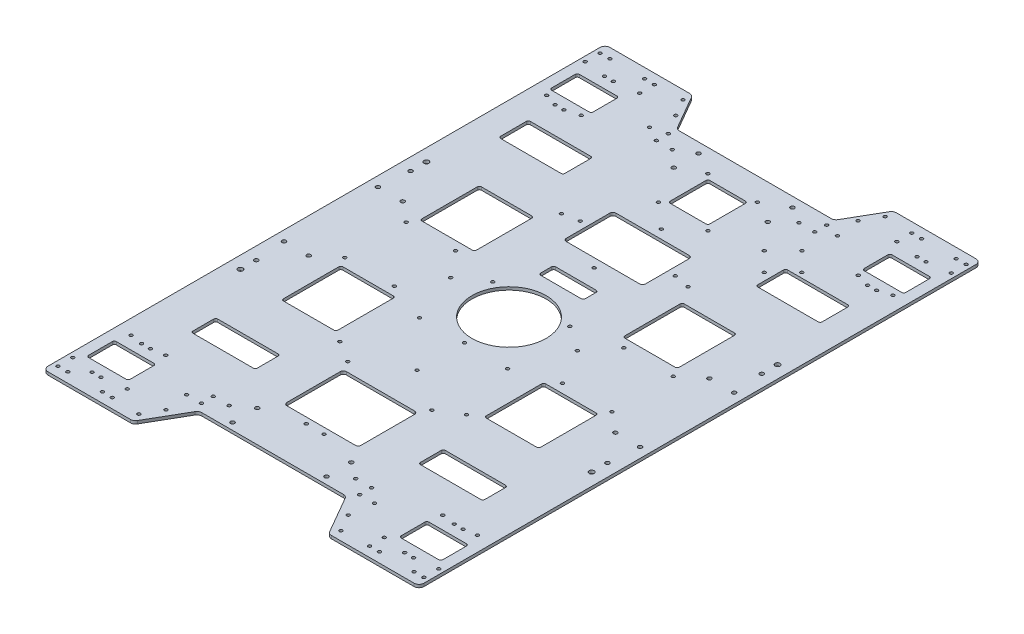
SolidWorks part; units mm, degrees
material "Hexcel AS4C (3000 丝)"
ref_plane "前视基准面" through (0, 0, 0) normal (0, 0, 1) x (1, 0, 0)
ref_plane "上视基准面" through (0, 0, 0) normal (0, 1, 0) x (1, 0, 0)
ref_plane "右视基准面" through (0, 0, 0) normal (1, 0, 0) x (0, 0, -1)
sketch "草图1" plane through (0, 0, 0) normal (0, 1, 0) x (1, 0, 0)
  line L0 (0, 420.0815) -> (0, -400.8011) construction
  line L1 (190, 287) -> (101.545, 287)
  line L2 (190, 287) -> (190, 0)
  line L3 (190, -281) -> (144.0917, -281)
  line L4 (-190, 287) -> (-190, 0)
  line L5 (-313.6361, 0) -> (397.123, 0) construction
  line L6 (144.0917, -281) -> (98.6603, -281)
  line L7 (-101.545, 287) -> (-79.6057, 249)
  line L8 (-79.6057, 249) -> (79.6057, 249)
  line L9 (79.6057, 249) -> (101.545, 287)
  line L10 (-98.6603, -281) -> (-74.4115, -239)
  line L12 (-74.4115, -239) -> (74.4115, -239)
  line L13 (-144.0917, -281) -> (-190, -281)
  line L14 (-101.545, 287) -> (-190, 287)
  line L15 (-98.6603, -281) -> (-144.0917, -281)
  line L17 (190, 0) -> (190, -281)
  line L20 (190, 287) -> (190, -281) construction
  line L22 (74.4115, -239) -> (98.6603, -281)
  line L24 (-190, 0) -> (-190, -281)
  line L26 (-190, 287) -> (-190, -281) construction
  line L44 (229.3448, 326.3448) -> (229.3448, -320.3448) construction
  line L45 (-229.3448, 326.3448) -> (-229.3448, -320.3448) construction
  line L46 (-78.8293, 326.3448) -> (-229.3448, 326.3448) construction
  line L47 (-78.8293, 326.3448) -> (-56.89, 288.3448) construction
  line L48 (-56.89, 288.3448) -> (56.89, 288.3448) construction
  line L49 (56.89, 288.3448) -> (78.8293, 326.3448) construction
  line L50 (229.3448, 326.3448) -> (78.8293, 326.3448) construction
  line L51 (-121.376, -320.3448) -> (-229.3448, -320.3448) construction
  line L52 (229.3448, -320.3448) -> (121.376, -320.3448) construction
  line L53 (-98.6603, -281) -> (-121.376, -320.3448) construction
  line L54 (98.6603, -281) -> (121.376, -320.3448) construction
  line L55 (-132.7338, -261.3276) -> (-144.0917, -281) construction
  line L56 (-132.7338, -261.3276) -> (-97.1273, -199.6552) construction
  line L57 (-97.1273, -199.6552) -> (97.1273, -199.6552) construction
  line L58 (97.1273, -199.6552) -> (132.7338, -261.3276) construction
  line L59 (132.7338, -261.3276) -> (144.0917, -281) construction
  point P0 (0, 0)
  point P10 (-110.2073, -274)
  point P13 (-79.8964, -221.5)
  point P14 (79.8964, -221.5)
  point P16 (110.2073, -274)
  point P21 (200, -271.5)
  point P22 (200, 291.5)
  point P23 (-145.7725, 287)
  point P24 (77.0076, 246.5)
  point P25 (-77.0076, 246.5)
  point P27 (-200, 291.5)
  point P28 (-200, -271.5)
  dimension "D1" = 568
  dimension "D2" = 380
  dimension "D3" = 38
  dimension "D4" = 197.3205
  dimension "D5" = 120
  dimension "D6" = 60
  dimension "D7" = 203.09
  dimension "D8" = 42
  dimension "D9" = 287
extrude "基本板" add sketch "草图1" along normal blind 3
sketch "草图2" plane through (0, 3, 0) normal (0, 1, 0) x (1, 0, 0)
  circle A0 centre (0, 0) radius 37.5
  circle A1 centre (38.9711, 22.5) radius 1.6
  circle A3 centre (0, 0) radius 37.5
  circle A5 centre (0, -45) radius 1.6
  circle A6 centre (0, 0) radius 37.5
  circle A7 centre (-38.9711, 22.5) radius 1.6
  point P14 (0, 0)
  point P16 (0, 0)
  dimension "D1" = 75
  dimension "D3" = 3.2
  dimension "D2" = 45
  dimension "D4" = 3
extrude "云台孔" cut sketch "草图2" against normal blind 3 contours A1 | A0 | A5 | A7 region at (0, 3, 0) region at (38.9711, 3, -22.5) region at (0, 3, 45) region at (-38.9711, 3, -22.5)
sketch "草图8" plane through (0, 3, 0) normal (0, 1, 0) x (1, 0, 0)
  line L0 (0, 320.5112) -> (0, -345.0597) construction
  line L13 (82.5, -149) -> (147.5, -149)
  line L14 (-82.5, -149) -> (-147.5, -149)
  line L15 (-82.5, -149) -> (-82.5, -174)
  line L16 (-82.5, -174) -> (-147.5, -174)
  line L17 (-147.5, -149) -> (-147.5, -174)
  line L18 (-82.5, -149) -> (-147.5, -174) construction
  line L19 (-82.5, -174) -> (-147.5, -149) construction
  line L20 (147.5, -149) -> (147.5, -174)
  line L21 (82.5, -149) -> (147.5, -174) construction
  line L22 (82.5, -174) -> (147.5, -149) construction
  line L23 (82.5, -149) -> (82.5, -174)
  line L24 (82.5, -174) -> (147.5, -174)
  point P12 (-115, -161.5)
  dimension "D1" = 230
  dimension "D5" = 174
  dimension "D7" = 25
  dimension "D8" = 65
extrude "减重过线孔" cut sketch "草图8" against normal blind 3
sketch "草图41" plane through (0, 3, 0) normal (0, 1, 0) x (1, 0, 0)
  line L0 (0, 188.4867) -> (0, -152.142) construction
  line L1 (-206.7892, 0) -> (229.7274, 0) construction
  line L2 (-130, 100) -> (-75, 100)
  line L3 (-130, 100) -> (-130, 40)
  line L4 (-130, 40) -> (-75, 40)
  line L5 (-75, 100) -> (-75, 40)
  line L6 (75, 100) -> (75, 40)
  line L7 (130, 40) -> (75, 40)
  line L8 (130, 100) -> (130, 40)
  line L9 (130, 100) -> (75, 100)
  line L10 (130, -100) -> (75, -100)
  line L11 (130, -100) -> (130, -40)
  line L12 (130, -40) -> (75, -40)
  line L13 (75, -100) -> (75, -40)
  line L14 (-75, -100) -> (-75, -40)
  line L15 (-130, -40) -> (-75, -40)
  line L16 (-130, -100) -> (-130, -40)
  line L17 (-130, -100) -> (-75, -100)
  dimension "D1" = 40
  dimension "D2" = 75
  dimension "D3" = 55
  dimension "D4" = 60
extrude "减重过线孔2" cut sketch "草图41" against normal blind 10
sketch "草图10" plane through (0, 3, 0) normal (0, 1, 0) x (1, 0, 0)
  line L0 (0, 320.3944) -> (0, -95.0551) construction
  line L1 (-162.5, 182) -> (-97.5, 182)
  line L2 (-162.5, 182) -> (-162.5, 152)
  line L3 (-162.5, 152) -> (-97.5, 152)
  line L4 (-97.5, 182) -> (-97.5, 152)
  line L5 (-162.5, 182) -> (-97.5, 152) construction
  line L6 (-162.5, 152) -> (-97.5, 182) construction
  line L7 (162.5, 152) -> (97.5, 152)
  line L8 (97.5, 152) -> (97.5, 182)
  line L9 (97.5, 182) -> (162.5, 182)
  line L11 (162.5, 182) -> (162.5, 152)
  point P0 (-130, 167)
  dimension "D1" = 65
  dimension "D2" = 30
  dimension "D3" = 167
  dimension "D4" = 130
  dimension "D5" = 65
extrude "后电机过线孔" cut sketch "草图10" against normal blind 3
sketch "草图11" plane through (0, 3, 0) normal (0, 1, 0) x (1, 0, 0)
  line L0 (-190, 287) -> (-190, -281) construction
  line L1 (-179, 248) -> (-137, 248)
  line L2 (-179, 248) -> (-179, 220)
  line L3 (-179, 220) -> (-137, 220)
  line L4 (-137, 248) -> (-137, 220)
  line L5 (-179, 248) -> (-137, 220) construction
  line L6 (-179, 220) -> (-137, 248) construction
  line L8 (-158, 274.32) -> (-158, 185.5546) construction
  line L9 (-208.9066, 234) -> (-106.7696, 234) construction
  line L10 (-264.4169, 0) -> (335.6364, 0) construction
  line L11 (0, 360.1922) -> (0, -386.7193) construction
  line L12 (179, 248) -> (179, 220)
  line L13 (179, 220) -> (137, 220)
  line L14 (137, 248) -> (137, 220)
  line L15 (179, 248) -> (137, 248)
  line L16 (179, -248) -> (137, -248)
  line L17 (137, -248) -> (137, -220)
  line L18 (179, -220) -> (137, -220)
  line L19 (179, -248) -> (179, -220)
  line L20 (-179, -248) -> (-179, -220)
  line L21 (-179, -220) -> (-137, -220)
  line L22 (-137, -248) -> (-137, -220)
  line L23 (-179, -248) -> (-137, -248)
  circle A0 centre (-153.5, 259) radius 1.6
  circle A1 centre (-162.5, 259) radius 1.6
  circle A2 centre (-153.5, 209) radius 1.6
  circle A3 centre (-162.5, 209) radius 1.6
  circle A4 centre (153.5, 259) radius 1.6
  circle A5 centre (162.5, 259) radius 1.6
  circle A6 centre (153.5, 209) radius 1.6
  circle A7 centre (162.5, 209) radius 1.6
  circle A8 centre (162.5, -209) radius 1.6
  circle A9 centre (153.5, -209) radius 1.6
  circle A10 centre (162.5, -259) radius 1.6
  circle A11 centre (153.5, -259) radius 1.6
  circle A12 centre (-162.5, -209) radius 1.6
  circle A13 centre (-153.5, -209) radius 1.6
  circle A14 centre (-153.5, -259) radius 1.6
  circle A15 centre (-162.5, -259) radius 1.6
  point P0 (-158, 234)
  dimension "D5" = 3.2
  dimension "D1" = 42
  dimension "D2" = 28
  dimension "D3" = 32
  dimension "D4" = 468
  dimension "D6" = 4.5
  dimension "D7" = 25
extrude "悬挂过孔" cut sketch "草图11" against normal blind 3
sketch "草图13" plane through (0, 3, 0) normal (0, 1, 0) x (1, 0, 0)
  line L0 (79.6057, 249) -> (-79.6057, 249) construction
  line L1 (25, 226) -> (-25, 226) construction
  line L2 (25, 226) -> (25, 176) construction
  line L3 (25, 176) -> (-25, 176) construction
  line L4 (-25, 226) -> (-25, 176) construction
  line L5 (25, 226) -> (-25, 176) construction
  line L6 (25, 176) -> (-25, 226) construction
  circle A0 centre (25, 176) radius 1.6
  circle A1 centre (25, 226) radius 1.6
  circle A2 centre (-25, 226) radius 1.6
  circle A3 centre (-25, 176) radius 1.6
  point P0 (0, 201)
  dimension "D1" = 3.2
  dimension "D2" = 50
  dimension "D3" = 48
  dimension "D4" = 50
extrude "原灯柱固定孔" cut sketch "草图13" against normal blind 3
sketch "草图14" plane through (0, 3, 0) normal (0, 1, 0) x (1, 0, 0)
  line L0 (0, 388.2914) -> (0, -299.2561) construction
  line L1 (79.6057, 249) -> (-79.6057, 249) construction
  line L4 (-74.4115, -239) -> (74.4115, -239) construction
  circle A0 centre (-47.5, 239) radius 2
  circle A1 centre (-47.5, 214) radius 2
  circle A2 centre (47.5, 214) radius 2
  circle A3 centre (47.5, 239) radius 2
  circle A4 centre (-47.5, -207) radius 2
  circle A5 centre (-47.5, -232) radius 2
  circle A6 centre (47.5, -232) radius 2
  circle A7 centre (47.5, -207) radius 2
  dimension "D1" = 25
  dimension "D3" = 4
  dimension "D4" = 4
  dimension "D6" = 4
  dimension "D7" = 4
  dimension "D2" = 10
  dimension "D5" = 47.5
  dimension "D8" = 25
  dimension "D9" = 7
  dimension "D10" = 95
extrude "前后装甲板固定孔" cut sketch "草图14" against normal blind 3
sketch "草图15" plane through (0, 3, 0) normal (0, 1, 0) x (1, 0, 0)
  line L0 (-212.3646, 0) -> (277.5556, 0) construction
  line L1 (190, -281) -> (190, 287) construction
  line L2 (0, 389.4336) -> (0, -385.931) construction
  circle A0 centre (155, 47.5) radius 2
  circle A1 centre (180, 47.5) radius 2
  circle A2 centre (180, -47.5) radius 2
  circle A3 centre (155, -47.5) radius 2
  circle A4 centre (-155, -47.5) radius 2
  circle A5 centre (-180, -47.5) radius 2
  circle A6 centre (-180, 47.5) radius 2
  circle A7 centre (-155, 47.5) radius 2
  dimension "D1" = 25
  dimension "D4" = 4
  dimension "D5" = 4
  dimension "D2" = 10
  dimension "D3" = 47.5
extrude "左右装甲板固定孔" cut sketch "草图15" against normal blind 3
sketch "草图16" plane through (0, 3, 0) normal (0, 1, 0) x (1, 0, 0)
  line L0 (0, 371.6115) -> (0, -351.9198) construction
  line L1 (79.6057, 249) -> (-79.6057, 249) construction
  line L2 (-74.4115, -239) -> (74.4115, -239) construction
  circle A0 centre (-64, 229) radius 1.6
  circle A1 centre (-64, 117) radius 1.6
  circle A2 centre (-64, 5) radius 1.6
  circle A3 centre (-64, -107) radius 1.6
  circle A4 centre (-64, -219) radius 1.6
  circle A5 centre (64, 229) radius 1.6
  circle A6 centre (64, -107) radius 1.6
  circle A7 centre (64, 5) radius 1.6
  circle A8 centre (64, 117) radius 1.6
  circle A9 centre (64, -219) radius 1.6
  dimension "D1" = 20
  dimension "D2" = 3.2
  dimension "D3" = 128
  dimension "D4" = 20
  dimension "D5" = 4
  dimension "D6" = 112
  dimension "D7" = 112
extrude "加强筋固定孔" cut sketch "草图16" against normal blind 3
sketch "草图17" plane through (0, 3, 0) normal (0, 1, 0) x (1, 0, 0)
  line L0 (134.2077, 331.9193) -> (53.2432, 191.6847) construction
  line L1 (101.545, 287) -> (79.6057, 249) construction
  line L2 (190, 287) -> (101.545, 287) construction
  line L3 (0, 408.349) -> (0, -455.0242) construction
  line L4 (-45.0771, -171.5407) -> (-117.5498, -297.067) construction
  line L5 (190, -281) -> (190, 287) construction
  line L6 (-190, -281) -> (-98.6603, -281) construction
  line L7 (-190, 287) -> (-190, -281) construction
  line L8 (-98.6603, -281) -> (-74.4115, -239) construction
  circle A0 centre (95, 264.0096) radius 1.6
  circle A1 centre (102.5, 277) radius 1.6
  circle A3 centre (-95, -258.0096) radius 1.6
  circle A4 centre (-102.5, -271) radius 1.6
  circle A7 centre (102.5, -271) radius 1.6
  circle A8 centre (95, -258.0096) radius 1.6
  circle A10 centre (-102.5, 277) radius 1.6
  circle A11 centre (-95, 264.0096) radius 1.6
  dimension "D2" = 15
  dimension "D4" = 3.2
  dimension "D5" = 3.2
  dimension "D6" = 95
  dimension "D11" = 3.2
  dimension "D12" = 3.2
  dimension "D3" = 95
  dimension "D8" = 10
  dimension "D14" = 10
  dimension "D16" = 15
extrude "前后挡片固定孔" [suppressed] cut sketch "草图17" against normal blind 3
sketch "草图18" plane through (0, 3, 0) normal (0, 1, 0) x (1, 0, 0)
  line L0 (325.6997, 0) -> (-414.0484, 0) construction
  line L1 (167.6795, 77.7768) -> (228.1621, 112.6965) construction
  line L2 (190, -281) -> (190, 287) construction
  line L3 (0, 334.7186) -> (0, -324.7689) construction
  line L4 (190, -281) -> (190, 287) construction
  circle A0 centre (167.6795, 77.7768) radius 1.6
  circle A1 centre (185, 87.7768) radius 1.6
  circle A2 centre (185, -87.7768) radius 1.6
  circle A3 centre (167.6795, -77.7768) radius 1.6
  circle A4 centre (-167.6795, -77.7768) radius 1.6
  circle A5 centre (-185, -87.7768) radius 1.6
  circle A6 centre (-185, 87.7768) radius 1.6
  circle A7 centre (-167.6795, 77.7768) radius 1.6
  point P24 (190, 90.6636)
  dimension "D1" = 30
  dimension "D5" = 3.2
  dimension "D6" = 3.2
  dimension "D2" = 181.3272
  dimension "D3" = 20
  dimension "D4" = 5
extrude "左右挡片固定孔" [suppressed] cut sketch "草图18" against normal blind 3
sketch "草图19" plane through (0, 3, 0) normal (0, 1, 0) x (1, 0, 0)
  line L0 (-190, 287) -> (-190, -281) construction
  line L2 (0, 300.5357) -> (0, -347.8075) construction
  line L3 (-284.3527, 0) -> (241.9977, 0) construction
  circle A0 centre (-177.5, -78) radius 2
  circle A1 centre (-177.5, -94) radius 2.5
  circle A2 centre (-177.5, 94) radius 2.5
  circle A3 centre (-177.5, 78) radius 2
  circle A4 centre (177.5, -94) radius 2.5
  circle A5 centre (177.5, -78) radius 2
  circle A6 centre (177.5, 78) radius 2
  circle A7 centre (177.5, 94) radius 2.5
  dimension "D1" = 12.5
  dimension "D3" = 4
  dimension "D4" = 5
  dimension "D2" = 188
  dimension "D5" = 16
extrude "纵车架固定孔" cut sketch "草图19" against normal blind 3
sketch "草图21" plane through (0, 3, 0) normal (0, 1, 0) x (1, 0, 0)
  line L1 (-84.0108, 0) -> (121.9234, 0) construction
  circle A0 centre (0, -93) radius 1.6
  dimension "D1" = 186
  dimension "D2" = 3.2
extrude "横车架固定孔" cut sketch "草图21" against normal blind 3
sketch "草图30" [suppressed] plane through (0, 3, 0) normal (0, 1, 0) x (1, 0, 0)
  line L0 (0, -74.9086) -> (0, -247.6971) construction
  line L1 (65, -113) -> (65, -157)
  line L2 (-77, -110) -> (-68, -110)
  line L3 (-80, -113) -> (-80, -157)
  line L4 (-77, -160) -> (-68, -160)
  line L5 (-65, -113) -> (-65, -157)
  line L6 (77, -160) -> (68, -160)
  line L7 (80, -113) -> (80, -157)
  line L8 (77, -110) -> (68, -110)
  arc A0 (-68, -110) -> (-65, -113) centre (-68, -113) cw
  arc A1 (-80, -157) -> (-77, -160) centre (-77, -157) ccw
  arc A2 (-68, -160) -> (-65, -157) centre (-68, -157) ccw
  arc A3 (-77, -110) -> (-80, -113) centre (-77, -113) ccw
  arc A4 (77, -110) -> (80, -113) centre (77, -113) cw
  arc A5 (68, -160) -> (65, -157) centre (68, -157) cw
  arc A6 (80, -157) -> (77, -160) centre (77, -157) cw
  arc A7 (68, -110) -> (65, -113) centre (68, -113) ccw
  point P11 (-65, -110)
  point P14 (-80, -160)
  point P17 (-65, -160)
  dimension "D5" = 3
  dimension "D1" = 50
  dimension "D2" = 15
  dimension "D3" = 130
  dimension "D4" = 110
sketch "草图32" plane through (0, 3, 0) normal (0, 1, 0) x (1, 0, 0)
  line L0 (0, -130.9301) -> (0, -286.8622) construction
  line L2 (-34.5, -190) -> (34.5, -190)
  line L3 (-37.5, -187) -> (-37.5, -133)
  line L4 (-34.5, -130) -> (34.5, -130)
  line L5 (37.5, -187) -> (37.5, -133)
  line L6 (0, -130) -> (0, -190) construction
  line L7 (-37.5, -160) -> (37.5, -160) construction
  arc A0 (34.5, -190) -> (37.5, -187) centre (34.5, -187) ccw
  arc A1 (-37.5, -133) -> (-34.5, -130) centre (-34.5, -133) cw
  arc A2 (-34.5, -190) -> (-37.5, -187) centre (-34.5, -187) cw
  arc A3 (34.5, -130) -> (37.5, -133) centre (34.5, -133) cw
  point P3 (0, -160)
  point P9 (37.5, -190)
  point P15 (-37.5, -130)
  point P18 (-37.5, -190)
  dimension "D4" = 3
  dimension "D1" = 60
  dimension "D2" = 75
  dimension "D3" = 160
extrude "切除-拉伸9" cut sketch "草图32" against normal blind 10
sketch "草图33" plane through (0, 3, 0) normal (0, 1, 0) x (1, 0, 0)
  line L1 (-70.5, -55) -> (70.5, -55) construction
  line L2 (-70.5, -55) -> (-70.5, -186) construction
  line L3 (-70.5, -186) -> (70.5, -186) construction
  line L4 (70.5, -55) -> (70.5, -186) construction
  line L5 (0, -186) -> (0, -55) construction
  line L6 (-70.5, -120.5) -> (70.5, -120.5) construction
  line L7 (-60, -180.5) -> (60, -180.5) construction
  line L8 (-60, -180.5) -> (-60, -60.5) construction
  line L9 (-60, -60.5) -> (60, -60.5) construction
  line L10 (60, -180.5) -> (60, -60.5) construction
  line L11 (0, -60.5) -> (0, -180.5) construction
  line L12 (-60, -120.5) -> (60, -120.5) construction
  circle A0 centre (-60, -180.5) radius 1.6 construction
  circle A1 centre (60, -180.5) radius 1.6 construction
  circle A2 centre (60, -60.5) radius 1.6 construction
  circle A3 centre (-60, -60.5) radius 1.6 construction
  circle A4 centre (-42.5, -120.5) radius 1.6
  circle A5 centre (42.5, -120.5) radius 1.6
  point P0 (0, -120.5)
  point P4 (0, -120.5)
  dimension "D6" = 3.2
  dimension "D7" = 3.2
  dimension "D8" = 3.2
  dimension "D9" = 3.2
  dimension "D10" = 3.2
  dimension "D11" = 85
  dimension "D1" = 131
  dimension "D2" = 141
  dimension "D3" = 55
  dimension "D4" = 120
  dimension "D5" = 120
extrude "PC座固定孔" cut sketch "草图33" against normal blind 10
sketch "草图36" plane through (0, 3, 0) normal (0, 1, 0) x (1, 0, 0)
  line L0 (-237.1174, 0) -> (284.0197, 0) construction
  line L1 (0, 354.7574) -> (0, -284.8649) construction
  line L2 (-74.4115, -239) -> (74.4115, -239) construction
  line L4 (79.6057, 249) -> (-79.6057, 249) construction
  circle A0 centre (-80, -231) radius 1.6
  circle A1 centre (-80, -219) radius 1.6
  circle A2 centre (80, -219) radius 1.6
  circle A3 centre (80, -231) radius 1.6
  circle A4 centre (-80, 241) radius 1.6
  circle A5 centre (-80, 229) radius 1.6
  circle A6 centre (80, 229) radius 1.6
  circle A7 centre (80, 241) radius 1.6
  dimension "D1" = 3.2
  dimension "D2" = 3.2
  dimension "D4" = 8
  dimension "D6" = 3.2
  dimension "D3" = 12
  dimension "D5" = 160
  dimension "D7" = 8
  dimension "D9" = 160
  dimension "D10" = 12
  dimension "D8" = 2
extrude "前后防撞架固定孔" cut sketch "草图36" against normal through all
sketch "草图29" plane through (0, 3, 0) normal (0, 1, 0) x (1, 0, 0)
  line L1 (40, 98) -> (40, 142)
  line L2 (37, 95) -> (-37, 95)
  line L3 (-40, 98) -> (-40, 142)
  line L4 (37, 145) -> (-37, 145)
  line L5 (-40, 120) -> (40, 120) construction
  line L6 (0, 95) -> (0, 145) construction
  arc A0 (40, 142) -> (37, 145) centre (37, 142) ccw
  arc A1 (-37, 95) -> (-40, 98) centre (-37, 98) cw
  arc A2 (40, 98) -> (37, 95) centre (37, 98) cw
  arc A3 (-40, 142) -> (-37, 145) centre (-37, 142) cw
  circle A4 centre (48, 120) radius 1.6
  circle A5 centre (0, 86) radius 1.6
  circle A6 centre (0, 154) radius 1.6
  circle A7 centre (-48, 120) radius 1.6
  point P0 (0, 120)
  point P6 (40, 145)
  point P12 (-40, 95)
  point P15 (40, 95)
  dimension "D4" = 3
  dimension "D5" = 3.2
  dimension "D7" = 3.2
  dimension "D8" = 68
  dimension "D1" = 80
  dimension "D2" = 50
  dimension "D3" = 120
  dimension "D6" = 96
extrude "电池座固定孔" cut sketch "草图29" against normal blind 10
sketch "草图39" plane through (0, 3, 0) normal (0, 1, 0) x (1, 0, 0)
  line L0 (185, -224.8149) -> (185, -286) construction
  line L1 (190, -281) -> (190, 287) construction
  line L2 (130, -286) -> (185, -286) construction
  line L3 (98.6603, -281) -> (190, -281) construction
  line L4 (130, -224.8149) -> (130, -286) construction
  line L5 (0, -68.0168) -> (0, -303.6758) construction
  line L6 (-288.2309, 3) -> (310.1394, 3) construction
  line L7 (130, 230.8149) -> (130, 292) construction
  line L8 (130, 292) -> (185, 292) construction
  line L9 (185, 230.8149) -> (185, 292) construction
  line L10 (190, 287) -> (101.545, 287) construction
  line L11 (157.5, -286) -> (157.5, -234.7139) construction
  circle A0 centre (185, -271) radius 1.6
  circle A1 centre (185, -256) radius 1.6
  circle A2 centre (130, -256) radius 1.6
  circle A3 centre (130, -271) radius 1.6
  circle A4 centre (-130, -271) radius 1.6
  circle A5 centre (-130, -256) radius 1.6
  circle A6 centre (-185, -256) radius 1.6
  circle A7 centre (-185, -271) radius 1.6
  circle A8 centre (-130, 262) radius 1.6
  circle A9 centre (-130, 277) radius 1.6
  circle A10 centre (185, 262) radius 1.6
  circle A11 centre (185, 277) radius 1.6
  circle A12 centre (-185, 277) radius 1.6
  circle A13 centre (-185, 262) radius 1.6
  circle A14 centre (130, 277) radius 1.6
  circle A15 centre (130, 262) radius 1.6
  dimension "D3" = 3.2
  dimension "D4" = 15
  dimension "D5" = 15
  dimension "D8" = 5
  dimension "D1" = 5
  dimension "D2" = 5
  dimension "D6" = 55
extrude "对角防撞架固定孔" cut sketch "草图39" against normal blind 10
sketch "草图42" plane through (0, 3, 0) normal (0, 1, 0) x (1, 0, 0)
  line L0 (-25, 226) -> (25, 176) construction
  line L1 (-25, 176) -> (25, 226) construction
  line L3 (-20, 221) -> (20, 221)
  line L4 (-20, 221) -> (-20, 181)
  line L5 (-20, 181) -> (20, 181)
  line L6 (20, 221) -> (20, 181)
  line L7 (0, 181) -> (0, 221) construction
  line L8 (-20, 201) -> (20, 201) construction
  point P8 (0, 201)
  dimension "D1" = 40
extrude "切除-拉伸11" cut sketch "草图42" against normal blind 10
sketch "草图43" plane through (0, 3, 0) normal (0, 1, 0) x (1, 0, 0)
  line L0 (0, 69.935) -> (0, -77.0754) construction
  line L1 (-56.3274, 0) -> (63.1225, 0) construction
  line L32 (75, 32.5) -> (75, -32.5) construction
  line L33 (81, 32.5) -> (81, -32.5)
  line L34 (69, 32.5) -> (69, -32.5)
  line L35 (95, 32.5) -> (95, -32.5) construction
  line L36 (101, 32.5) -> (101, -32.5)
  line L37 (89, 32.5) -> (89, -32.5)
  line L38 (115, 32.5) -> (115, -32.5) construction
  line L39 (121, 32.5) -> (121, -32.5)
  line L40 (109, 32.5) -> (109, -32.5)
  line L41 (135, 32.5) -> (135, -32.5) construction
  line L42 (141, 32.5) -> (141, -32.5)
  line L43 (129, 32.5) -> (129, -32.5)
  line L44 (-75, 32.5) -> (-75, -32.5) construction
  line L45 (-81, 32.5) -> (-81, -32.5)
  line L46 (-69, 32.5) -> (-69, -32.5)
  line L47 (-95, 32.5) -> (-95, -32.5) construction
  line L48 (-101, 32.5) -> (-101, -32.5)
  line L49 (-89, 32.5) -> (-89, -32.5)
  line L50 (-115, 32.5) -> (-115, -32.5) construction
  line L51 (-121, 32.5) -> (-121, -32.5)
  line L52 (-109, 32.5) -> (-109, -32.5)
  line L53 (-135, 32.5) -> (-135, -32.5) construction
  line L54 (-141, 32.5) -> (-141, -32.5)
  line L55 (-129, 32.5) -> (-129, -32.5)
  arc A0 (81, 32.5) -> (69, 32.5) centre (75, 32.5) ccw
  arc A1 (69, -32.5) -> (81, -32.5) centre (75, -32.5) ccw
  arc A5 (101, 32.5) -> (89, 32.5) centre (95, 32.5) ccw
  arc A6 (89, -32.5) -> (101, -32.5) centre (95, -32.5) ccw
  arc A7 (121, 32.5) -> (109, 32.5) centre (115, 32.5) ccw
  arc A8 (109, -32.5) -> (121, -32.5) centre (115, -32.5) ccw
  arc A9 (141, 32.5) -> (129, 32.5) centre (135, 32.5) ccw
  arc A10 (129, -32.5) -> (141, -32.5) centre (135, -32.5) ccw
  arc A11 (-81, 32.5) -> (-69, 32.5) centre (-75, 32.5) cw
  arc A12 (-69, -32.5) -> (-81, -32.5) centre (-75, -32.5) cw
  arc A13 (-101, 32.5) -> (-89, 32.5) centre (-95, 32.5) cw
  arc A14 (-89, -32.5) -> (-101, -32.5) centre (-95, -32.5) cw
  arc A15 (-121, 32.5) -> (-109, 32.5) centre (-115, 32.5) cw
  arc A16 (-109, -32.5) -> (-121, -32.5) centre (-115, -32.5) cw
  arc A17 (-141, 32.5) -> (-129, 32.5) centre (-135, 32.5) cw
  arc A18 (-129, -32.5) -> (-141, -32.5) centre (-135, -32.5) cw
  point P4 (75, 0)
  point P16 (95, 0)
  point P23 (115, 0)
  point P30 (135, 0)
  point P35 (-75, 0)
  point P42 (-95, 0)
  point P49 (-115, 0)
  point P57 (-135, 0)
  dimension "D1" = 4
  dimension "D4" = 75
  dimension "D5" = 20
  dimension "D2" = 12
  dimension "D3" = 65
extrude "切除-拉伸12" [suppressed] cut sketch "草图43" against normal blind 10
sketch "草图44" [suppressed] plane through (0, 3, 0) normal (0, 1, 0) x (1, 0, 0)
  line L0 (0, 99.1729) -> (0, -37.5) construction
  circle A0 centre (115, -264) radius 1.6
  circle A3 centre (185, -264) radius 1.6 construction
  circle A4 centre (185, -264) radius 1.6
  circle A5 centre (0, 0) radius 37.5 construction
  circle A6 centre (185, -231) radius 1.6
  circle A7 centre (185, 284) radius 1.6 construction
  circle A8 centre (185, 284) radius 1.6
  circle A9 centre (-115, -264) radius 1.6
  circle A10 centre (-185, -231) radius 1.6
  circle A11 centre (115, 284) radius 1.6
  circle A12 centre (185, 241) radius 1.6
  circle A13 centre (-185, 241) radius 1.6
  circle A14 centre (-115, 284) radius 1.6
  point P15 (0, 30.8364)
  dimension "D1" = 3.2
  dimension "D3" = 3.2
  dimension "D5" = 3.2
  dimension "D6" = 3.2
  dimension "D2" = 70
  dimension "D4" = 33
  dimension "D7" = 43
  dimension "D8" = 70
extrude "切除-拉伸13" [suppressed] cut sketch "草图44" against normal through all
sketch "草图34" plane through (0, 3, 0) normal (0, 1, 0) x (1, 0, 0)
  line L1 (71, 206) -> (109, 206) construction
  line L2 (71, 206) -> (71, 168) construction
  line L3 (71, 168) -> (109, 168) construction
  line L4 (109, 206) -> (109, 168) construction
  line L5 (90, 168) -> (90, 206) construction
  line L6 (71, 187) -> (109, 187) construction
  circle A0 centre (90, 168) radius 1.6
  circle A1 centre (71, 187) radius 1.6
  circle A2 centre (90, 206) radius 1.6
  circle A3 centre (109, 187) radius 1.6
  point P0 (90, 187)
  dimension "D2" = 3.2
  dimension "D3" = 3.2
  dimension "D4" = 3.2
  dimension "D7" = 3.2
  dimension "D1" = 38
  dimension "D5" = 90
  dimension "D6" = 187
extrude "UWB固定孔" cut sketch "草图34" against normal blind 10
sketch "草图47" plane through (0, 3, 0) normal (0, 1, 0) x (1, 0, 0)
  line L0 (0, 349.8553) -> (0, -296.5751) construction
  circle A0 centre (140, 277) radius 1.6
  circle A1 centre (185, -271) radius 1.6 construction
  circle A2 centre (185, -271) radius 1.6
  circle A3 centre (95, -231) radius 1.6
  circle A4 centre (175, -271) radius 1.6
  circle A5 centre (140, 213) radius 1.6
  circle A6 centre (175, -207) radius 1.6
  circle A7 centre (-140, -271) radius 1.6
  circle A8 centre (-140, -207) radius 1.6
  circle A9 centre (-175, 213) radius 1.6
  circle A10 centre (-95, 237) radius 1.6
  circle A11 centre (185, 277) radius 1.6 construction
  circle A12 centre (185, 277) radius 1.6
  circle A13 centre (175, 277) radius 1.6
  circle A14 centre (95, 237) radius 1.6
  circle A15 centre (175, 213) radius 1.6
  circle A16 centre (-175, 277) radius 1.6
  circle A17 centre (-185, 277) radius 1.6
  circle A18 centre (140, -207) radius 1.6
  circle A19 centre (140, -271) radius 1.6
  circle A20 centre (-175, -207) radius 1.6
  circle A21 centre (-140, 213) radius 1.6
  circle A22 centre (-175, -271) radius 1.6
  circle A23 centre (-95, -231) radius 1.6
  circle A24 centre (-185, -271) radius 1.6
  circle A25 centre (-140, 277) radius 1.6
  dimension "D3" = 3.2
  dimension "D6" = 3.2
  dimension "D8" = 64
  dimension "D10" = 3.2
  dimension "D13" = 3.2
  dimension "D2" = 3.2
  dimension "D9" = 3.2
  dimension "D16" = 2
  dimension "D19" = 35
  dimension "D4" = 80
  dimension "D5" = 40
  dimension "D7" = 64
  dimension "D11" = 40
  dimension "D12" = 80
  dimension "D14" = 10
  dimension "D15" = 10
  dimension "D17" = 35
  dimension "D18" = 2
extrude "救援固定孔" cut sketch "草图47" against normal through all
sketch "草图48" plane through (0, 3, 0) normal (0, 1, 0) x (1, 0, 0)
  line L0 (0, 63.9696) -> (0, -155.8034) construction
  circle A0 centre (-44.5, -46) radius 1.6
  circle A1 centre (44.5, -46) radius 1.6
  circle A2 centre (-9, -196) radius 1.6
  circle A3 centre (9, -196) radius 1.6
  dimension "D3" = 3.2
  dimension "D6" = 3.2
  dimension "D1" = 44.5
  dimension "D2" = 46
  dimension "D4" = 9
  dimension "D5" = 196
extrude "切除-拉伸14" cut sketch "草图48" against normal through all
sketch "草图50" plane through (0, 0, 0) normal (0, -1, 0) x (1, 0, 0)
  circle A0 centre (-99.3301, -275.8397) radius 1.5 construction
  circle A1 centre (-91.8301, -262.8494) radius 1.5 construction
  circle A2 centre (99.3301, -275.8397) radius 1.5 construction
  circle A3 centre (91.8301, -262.8494) radius 1.5 construction
  circle A4 centre (-99.3301, 269.8397) radius 1.5 construction
  circle A5 centre (-91.8301, 256.8494) radius 1.5 construction
  circle A6 centre (91.8301, 256.8494) radius 1.5 construction
  circle A7 centre (99.3301, 269.8397) radius 1.5 construction
  circle A8 centre (-99.3301, -275.8397) radius 1.5
  circle A9 centre (-91.8301, -262.8494) radius 1.5
  circle A10 centre (99.3301, -275.8397) radius 1.5
  circle A11 centre (91.8301, -262.8494) radius 1.5
  circle A12 centre (-99.3301, 269.8397) radius 1.5
  circle A13 centre (-91.8301, 256.8494) radius 1.5
  circle A14 centre (91.8301, 256.8494) radius 1.5
  circle A15 centre (99.3301, 269.8397) radius 1.5
extrude "切除-拉伸16" [suppressed] cut sketch "草图50" against normal blind 10
sketch "草图51" plane through (0, 3, 0) normal (0, 1, 0) x (1, 0, 0)
  line L0 (0, -15.6528) -> (0, -161.3511) construction
  line L2 (-20.5, 67.5) -> (20.5, 67.5)
  line L3 (-22.5, 65.5) -> (-22.5, 54.5)
  line L4 (-20.5, 52.5) -> (20.5, 52.5)
  line L5 (22.5, 65.5) -> (22.5, 54.5)
  line L6 (0, 52.5) -> (0, 67.5) construction
  line L7 (-22.5, 60) -> (22.5, 60) construction
  arc A0 (20.5, 67.5) -> (22.5, 65.5) centre (20.5, 65.5) cw
  arc A1 (-22.5, 54.5) -> (-20.5, 52.5) centre (-20.5, 54.5) ccw
  arc A2 (-20.5, 67.5) -> (-22.5, 65.5) centre (-20.5, 65.5) ccw
  arc A3 (20.5, 52.5) -> (22.5, 54.5) centre (20.5, 54.5) ccw
  point P3 (0, 60)
  point P9 (22.5, 67.5)
  point P15 (-22.5, 52.5)
  point P18 (-22.5, 67.5)
  dimension "D4" = 2
  dimension "D5" = 2
  dimension "D6" = 2
  dimension "D7" = 2
  dimension "D1" = 15
  dimension "D2" = 45
  dimension "D3" = 60
extrude "6623电机过线孔" cut sketch "草图51" against normal blind 10
fillet "外圆角" radius 5 12 edges at (-190, 1.5, -287) (-101.545, 1.5, -287) (-79.6057, 1.5, -249) (79.6057, 1.5, -249) (101.545, 1.5, -287) (190, 1.5, -287) (190, 1.5, 281) (98.6603, 1.5, 281) (74.4115, 1.5, 239) (-74.4115, 1.5, 239) (-98.6603, 1.5, 281) (-190, 1.5, 281)
fillet "内圆角" radius 2 52 edges at (-147.5, 1.5, 149) (-82.5, 1.5, 149) (-82.5, 1.5, 174) (-147.5, 1.5, 174) (82.5, 1.5, 149) (147.5, 1.5, 149) (147.5, 1.5, 174) (82.5, 1.5, 174) (-130, 1.5, -100) (-75, 1.5, -100) (-75, 1.5, -40) (-130, 1.5, -40) (-130, 1.5, 100) (-130, 1.5, 40) (-75, 1.5, 40) (-75, 1.5, 100) (130, 1.5, 100) (75, 1.5, 100) (75, 1.5, 40) (130, 1.5, 40) (130, 1.5, -100) (130, 1.5, -40) (75, 1.5, -40) (75, 1.5, -100) (-97.5, 1.5, -152) (-162.5, 1.5, -152) (-162.5, 1.5, -182) (-97.5, 1.5, -182) (162.5, 1.5, -182) (-137, 1.5, -220) (-179, 1.5, -220) (-179, 1.5, -248) (-137, 1.5, -248) (-179, 1.5, 220) (-137, 1.5, 220) (-137, 1.5, 248) (179, 1.5, 248) (137, 1.5, 248) (137, 1.5, 220) (179, 1.5, 220) (179, 1.5, -248) (179, 1.5, -220) (137, 1.5, -220) (137, 1.5, -248) (20, 1.5, -181) (-20, 1.5, -181) (-20, 1.5, -221) (20, 1.5, -221) (-179, 1.5, 248) (162.5, 1.5, -152) (97.5, 1.5, -152) (97.5, 1.5, -182)
sketch "草图52" plane through (0, 3, 0) normal (0, 1, 0) x (1, 0, 0)
  line L0 (0, 174.243) -> (0, -94.6) construction
  line L1 (80, 190) -> (80, 208) construction
  line L2 (-125.2, 190) -> (-80, 190) construction
  line L3 (-125.2, 190) -> (-125.2, 208) construction
  line L4 (-125.2, 208) -> (-80, 208) construction
  line L5 (-80, 190) -> (-80, 208) construction
  line L6 (125.2, 208) -> (80, 208) construction
  line L7 (125.2, 190) -> (125.2, 208) construction
  line L8 (125.2, 190) -> (80, 190) construction
  line L13 (-85, -130) -> (-130.2, -130) construction
  line L14 (85, -121) -> (130.2, -121) construction
  line L15 (85, -121) -> (85, -139) construction
  line L16 (85, -139) -> (130.2, -139) construction
  line L17 (130.2, -121) -> (130.2, -139) construction
  line L18 (107.6, -139) -> (107.6, -121) construction
  line L19 (85, -130) -> (130.2, -130) construction
  line L20 (-107.6, -139) -> (-107.6, -121) construction
  line L21 (-130.2, -121) -> (-130.2, -139) construction
  line L22 (-85, -139) -> (-130.2, -139) construction
  line L23 (-85, -121) -> (-85, -139) construction
  line L24 (-85, -121) -> (-130.2, -121) construction
  circle A0 centre (-125.2, 190) radius 1.6
  circle A1 centre (-80, 190) radius 1.6
  circle A2 centre (-80, 208) radius 1.6
  circle A3 centre (-125.2, 208) radius 1.6
  circle A4 centre (125.2, 208) radius 1.6
  circle A5 centre (80, 208) radius 1.6
  circle A6 centre (80, 190) radius 1.6
  circle A7 centre (125.2, 190) radius 1.6
  circle A9 centre (85, -139) radius 1.6
  circle A10 centre (130.2, -139) radius 1.6
  circle A11 centre (130.2, -121) radius 1.6
  circle A12 centre (85, -121) radius 1.6
  circle A13 centre (-85, -121) radius 1.6
  circle A14 centre (-130.2, -121) radius 1.6
  circle A15 centre (-130.2, -139) radius 1.6
  circle A16 centre (-85, -139) radius 1.6
  circle A17 centre (0, -93) radius 1.6 construction
  point P29 (107.6, -130)
  point P55 (-106.25, -130)
  dimension "D3" = 2
  dimension "D10" = 3.2
  dimension "D4" = 2
  dimension "D2" = 3.2
  dimension "D6" = 2
  dimension "D7" = 45.2
  dimension "D8" = 18
  dimension "D9" = 45.2
  dimension "D13" = 2
  dimension "D11" = 170
  dimension "D12" = 130
  dimension "D14" = 80
  dimension "D5" = 18
  dimension "D15" = 190
extrude "3508电调固定孔" [suppressed] cut sketch "草图52" against normal blind 10
sketch "草图53" plane through (0, 3, 0) normal (0, 1, 0) x (1, 0, 0)
  line L0 (0, -84.1974) -> (0, 49.8195) construction
  line L1 (-135, 31) -> (-85, 31) construction
  line L2 (-135, 31) -> (-135, -31) construction
  line L3 (-135, -31) -> (-85, -31) construction
  line L4 (-85, 31) -> (-85, -31) construction
  line L5 (-110, -31) -> (-110, 31) construction
  line L6 (-135, 0) -> (-85, 0) construction
  line L7 (135, 0) -> (85, 0) construction
  line L8 (110, -31) -> (110, 31) construction
  line L9 (85, 31) -> (85, -31) construction
  line L10 (135, -31) -> (85, -31) construction
  line L11 (135, 31) -> (135, -31) construction
  line L12 (135, 31) -> (85, 31) construction
  circle A0 centre (-135, -31) radius 1.6
  circle A1 centre (-85, -31) radius 1.6
  circle A2 centre (-85, 31) radius 1.6
  circle A3 centre (-135, 31) radius 1.6
  circle A4 centre (135, 31) radius 1.6
  circle A5 centre (85, 31) radius 1.6
  circle A6 centre (85, -31) radius 1.6
  circle A7 centre (135, -31) radius 1.6
  point P0 (-110, 0)
  point P26 (110, 0)
  dimension "D3" = 3.2
  dimension "D1" = 62
  dimension "D2" = 50
  dimension "D4" = 110
extrude "RFID固定孔" cut sketch "草图53" against normal blind 10
sketch "草图54" plane through (0, 0, 0) normal (0, -1, 0) x (1, 0, 0)
  line L0 (-263.9822, -3) -> (389.5678, -3) construction
  line L1 (0, -107.2403) -> (0, -312.9663) construction
  line L2 (-102.1224, -278) -> (-92.1224, -260.6795) construction
  line L3 (-81.0491, -251.5) -> (-100.1016, -284.5) construction
  line L4 (-104.4318, -287) -> (-185, -287) construction
  line L5 (102.1224, -278) -> (92.1224, -260.6795) construction
  line L6 (102.1224, 272) -> (92.1224, 254.6795) construction
  line L7 (-102.1224, 272) -> (-92.1224, 254.6795) construction
  line L8 (-185, 281) -> (-101.547, 281) construction
  circle A0 centre (-102.1224, -278) radius 1.6
  circle A1 centre (-92.1224, -260.6795) radius 1.6
  circle A2 centre (92.1224, -260.6795) radius 1.6
  circle A3 centre (102.1224, -278) radius 1.6
  circle A4 centre (102.1224, 272) radius 1.6
  circle A5 centre (92.1224, 254.6795) radius 1.6
  circle A6 centre (-92.1224, 254.6795) radius 1.6
  circle A7 centre (-102.1224, 272) radius 1.6
  dimension "D1" = 3.2
  dimension "D2" = 3.2
  dimension "D3" = 5
  dimension "D4" = 9
  dimension "D5" = 20
  dimension "D6" = 9
extrude "挡片固定孔" cut sketch "草图54" against normal blind 10
